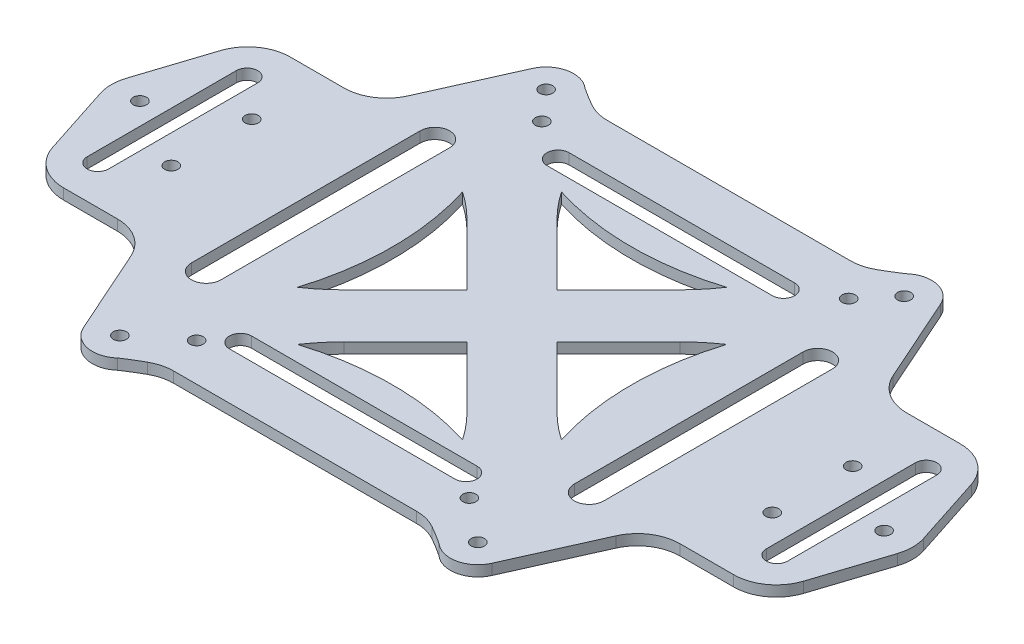
SolidWorks part; units mm, degrees
material "PPS"
ref_plane "前视基准面" through (0, 0, 0) normal (0, 0, 1) x (1, 0, 0)
ref_plane "上视基准面" through (0, 0, 0) normal (0, 1, 0) x (1, 0, 0)
ref_plane "右视基准面" through (0, 0, 0) normal (1, 0, 0) x (0, 0, -1)
sketch "参考" plane through (0, 0, 0) normal (0, 1, 0) x (1, 0, 0)
  line L3 (-133.7177, 0) -> (146.3754, 0) construction
  line L56 (0, 96.0639) -> (0, -115.1457) construction
  line L177 (114.5911, 7.4683) -> (114.5911, -7.4683)
  line L178 (114.5911, 7.4683) -> (43.1936, 17.6463)
  line L179 (114.5911, -7.4683) -> (43.1936, -17.6463)
  line L180 (-114.5911, -7.4683) -> (-43.1936, -17.6463)
  line L181 (-114.5911, 7.4683) -> (-114.5911, -7.4683)
  line L182 (-114.5911, 7.4683) -> (-43.1936, 17.6463)
  arc A18 (-37.7098, 54.831) -> (37.7098, 54.831) centre (0, 111.5317) ccw
  arc A20 (48.2756, 48.4632) -> (43.1936, 17.6463) centre (246.1791, 0) ccw
  arc A21 (48.2756, 48.4632) -> (37.7098, 54.831) centre (42, 50) ccw
  arc A22 (-37.7098, -54.831) -> (37.7098, -54.831) centre (0, -111.5317) cw
  arc A23 (48.2756, -48.4632) -> (43.1936, -17.6463) centre (246.1791, 0) cw
  arc A24 (48.2756, -48.4632) -> (37.7098, -54.831) centre (42, -50) cw
  arc A26 (-48.2756, -48.4632) -> (-37.7098, -54.831) centre (-42, -50) ccw
  arc A27 (-48.2756, -48.4632) -> (-43.1936, -17.6463) centre (-246.1791, 0) ccw
  arc A28 (-48.2756, 48.4632) -> (-37.7098, 54.831) centre (-42, 50) cw
  arc A30 (-48.2756, 48.4632) -> (-43.1936, 17.6463) centre (-246.1791, 0) cw
  dimension "D11" = 50
  dimension "D12" = 42
sketch "草图1" plane through (0, 0, 0) normal (0, 1, 0) x (1, 0, 0)
  line L0 (-160.1541, 0) -> (172.3115, 0) construction
  line L1 (0, 124.2182) -> (0, -143.4382) construction
  line L2 (79.6696, -17.5) -> (79.6696, 17.5) construction
  line L3 (77.1696, -17.5) -> (77.1696, 17.5)
  line L4 (82.1696, -17.5) -> (82.1696, 17.5)
  line L5 (-133.7177, 0) -> (146.3754, 0) construction
  line L6 (47.9, 52.6334) -> (59.525, 26.5883)
  line L7 (59.525, 26.5883) -> (85.8696, 26.5883)
  line L8 (85.8696, 26.5883) -> (94.5058, 0)
  line L9 (59.525, -26.5883) -> (85.8696, -26.5883)
  line L10 (47.9, -52.6334) -> (59.525, -26.5883)
  line L11 (85.8696, -26.5883) -> (94.5058, 0)
  line L12 (-47.9, -52.6334) -> (-59.525, -26.5883)
  line L13 (-59.525, -26.5883) -> (-85.8696, -26.5883)
  line L14 (-85.8696, -26.5883) -> (-94.5058, 0)
  line L15 (-85.8696, 26.5883) -> (-94.5058, 0)
  line L16 (-47.9, 52.6334) -> (-59.525, 26.5883)
  line L17 (-59.525, 26.5883) -> (-85.8696, 26.5883)
  line L18 (-79.6696, -17.5) -> (-79.6696, 17.5) construction
  line L19 (-77.1696, -17.5) -> (-77.1696, 17.5)
  line L20 (-82.1696, -17.5) -> (-82.1696, 17.5)
  line L21 (-24.996, 14.4296) -> (-10.5664, 0)
  line L22 (14.4296, 24.996) -> (0, 10.5664)
  line L23 (-24.996, -14.4296) -> (-10.5664, 0)
  line L24 (-14.4296, 24.996) -> (0, 10.5664)
  line L25 (0, 96.0639) -> (0, -115.1457) construction
  line L26 (24.996, -14.4296) -> (10.5664, 0)
  line L27 (24.996, 14.4296) -> (10.5664, 0)
  line L28 (-14.4296, -24.996) -> (0, -10.5664)
  line L29 (14.4296, -24.996) -> (0, -10.5664)
  line L30 (44.9192, -26.8293) -> (44.9192, 26.8293) construction
  line L31 (41.4687, -26.8293) -> (41.4687, 26.8293)
  line L32 (48.3697, -26.8293) -> (48.3697, 26.8293)
  line L33 (-26.4535, -37.2441) -> (26.4535, -37.2441) construction
  line L34 (-26.4535, -34.637) -> (26.4535, -34.637)
  line L35 (-26.4535, -39.8513) -> (26.4535, -39.8513)
  line L36 (-26.4535, 37.2441) -> (26.4535, 37.2441) construction
  line L37 (-26.4535, 34.637) -> (26.4535, 34.637)
  line L38 (-26.4535, 39.8513) -> (26.4535, 39.8513)
  line L39 (-44.9192, -26.8293) -> (-44.9192, 26.8293) construction
  line L40 (-41.4687, -26.8293) -> (-41.4687, 26.8293)
  line L41 (-48.3697, -26.8293) -> (-48.3697, 26.8293)
  line L42 (-30.9782, 50.8906) -> (30.9782, 50.8906)
  line L43 (-30.9782, -50.8906) -> (30.9782, -50.8906)
  circle A6 centre (42, 50) radius 1.55
  circle A7 centre (42, -50) radius 1.55
  circle A8 centre (-42, -50) radius 1.55
  circle A9 centre (-42, 50) radius 1.55
  circle A10 centre (36, 43) radius 1.55
  circle A11 centre (32, -42) radius 1.55
  circle A12 centre (-32, -42) radius 1.55
  circle A13 centre (-36, 43) radius 1.55
  arc A14 (47.9, 52.6334) -> (37.7098, 54.831) centre (42, 50) ccw
  arc A15 (-37.7098, 54.831) -> (-30.9782, 50.8906) centre (0, 111.5317) ccw
  arc A18 (77.1696, -17.5) -> (82.1696, -17.5) centre (79.6696, -17.5) ccw
  arc A19 (82.1696, 17.5) -> (77.1696, 17.5) centre (79.6696, 17.5) ccw
  circle A20 centre (70.5, 9.4358) radius 1.55
  circle A21 centre (70.5, -9.4358) radius 1.55
  circle A22 centre (-70.5, -9.4358) radius 1.55
  circle A23 centre (-70.5, 9.4358) radius 1.55
  circle A24 centre (87.3, 0) radius 1.55
  arc A25 (48.2756, 48.4632) -> (37.7098, 54.831) centre (42, 50) ccw construction
  arc A26 (47.9, -52.6334) -> (37.7098, -54.831) centre (42, -50) cw
  arc A27 (-37.7098, -54.831) -> (-30.9782, -50.8906) centre (0, -111.5317) cw
  arc A28 (-47.9, 52.6334) -> (-37.7098, 54.831) centre (-42, 50) cw
  arc A29 (-77.1696, -17.5) -> (-82.1696, -17.5) centre (-79.6696, -17.5) cw
  arc A30 (-82.1696, 17.5) -> (-77.1696, 17.5) centre (-79.6696, 17.5) cw
  circle A31 centre (-87.3, 0) radius 1.55
  arc A32 (-47.9, -52.6334) -> (-37.7098, -54.831) centre (-42, -50) ccw
  arc A33 (-24.996, 14.4296) -> (-30.9782, 19.3706) centre (-53.9062, -14.4807) ccw
  arc A34 (-24.996, -14.4296) -> (-30.9782, -19.3706) centre (-53.9062, 14.4807) cw
  arc A35 (-30.9782, -19.3706) -> (-30.9782, 19.3706) centre (-93.0146, 0) ccw
  arc A36 (-14.4296, 24.996) -> (-19.3706, 30.9782) centre (14.4807, 53.9062) cw
  arc A37 (-19.3706, 30.9782) -> (19.3706, 30.9782) centre (0, 93.0146) ccw
  arc A38 (14.4296, 24.996) -> (19.3706, 30.9782) centre (-14.4807, 53.9062) ccw
  arc A39 (24.996, 14.4296) -> (30.9782, 19.3706) centre (53.9062, -14.4807) cw
  arc A40 (30.9782, 19.3706) -> (30.9782, -19.3706) centre (93.0146, 0) ccw
  arc A41 (24.996, -14.4296) -> (30.9782, -19.3706) centre (53.9062, 14.4807) ccw
  arc A42 (14.4296, -24.996) -> (19.3706, -30.9782) centre (-14.4807, -53.9062) cw
  arc A43 (19.3706, -30.9782) -> (-19.3706, -30.9782) centre (0, -93.0146) ccw
  arc A44 (-14.4296, -24.996) -> (-19.3706, -30.9782) centre (14.4807, -53.9062) ccw
  arc A45 (41.4687, -26.8293) -> (48.3697, -26.8293) centre (44.9192, -26.8293) ccw
  arc A46 (48.3697, 26.8293) -> (41.4687, 26.8293) centre (44.9192, 26.8293) ccw
  arc A47 (-26.4535, -34.637) -> (-26.4535, -39.8513) centre (-26.4535, -37.2441) ccw
  arc A48 (26.4535, -39.8513) -> (26.4535, -34.637) centre (26.4535, -37.2441) ccw
  arc A49 (-26.4535, 34.637) -> (-26.4535, 39.8513) centre (-26.4535, 37.2441) cw
  arc A50 (26.4535, 39.8513) -> (26.4535, 34.637) centre (26.4535, 37.2441) cw
  arc A51 (-41.4687, -26.8293) -> (-48.3697, -26.8293) centre (-44.9192, -26.8293) cw
  arc A52 (-48.3697, 26.8293) -> (-41.4687, 26.8293) centre (-44.9192, 26.8293) cw
  arc A53 (30.9782, 50.8906) -> (37.7098, 54.831) centre (0, 111.5317) ccw
  arc A54 (30.9782, -50.8906) -> (37.7098, -54.831) centre (0, -111.5317) cw
  point P30 (79.6696, 0)
  point P63 (44.9192, 0)
  point P78 (-79.6696, 0)
  point P98 (0, 0)
  point P116 (0, -37.2441)
  point P129 (0, 37.2441)
  point P136 (-44.9192, 0)
  dimension "D1" = 50
  dimension "D3" = 3.1
  dimension "D8" = 2.5
  dimension "D10" = 3.1
  dimension "D12" = 3.1
  dimension "D2" = 42
  dimension "D4" = 36
  dimension "D5" = 32
  dimension "D6" = 42
  dimension "D7" = 43
  dimension "D9" = 35
  dimension "D11" = 70.5
  dimension "D13" = 87.3
  dimension "D14" = 4
extrude "凸台-拉伸1" add sketch "草图1" along normal blind 2.5
fillet "圆角1" radius 10 14 edges at (59.525, 1.25, -26.5883) (85.8696, 1.25, -26.5883) (85.8696, 1.25, 26.5883) (94.5058, 1.25, 0) (59.525, 1.25, 26.5883) (-59.525, 1.25, 26.5883) (-59.525, 1.25, -26.5883) (-85.8696, 1.25, -26.5883) (-85.8696, 1.25, 26.5883) (-94.5058, 1.25, 0) (30.9782, 1.25, -50.8906) (-30.9782, 1.25, -50.8906) (30.9782, 1.25, 50.8906) (-30.9782, 1.25, 50.8906)
